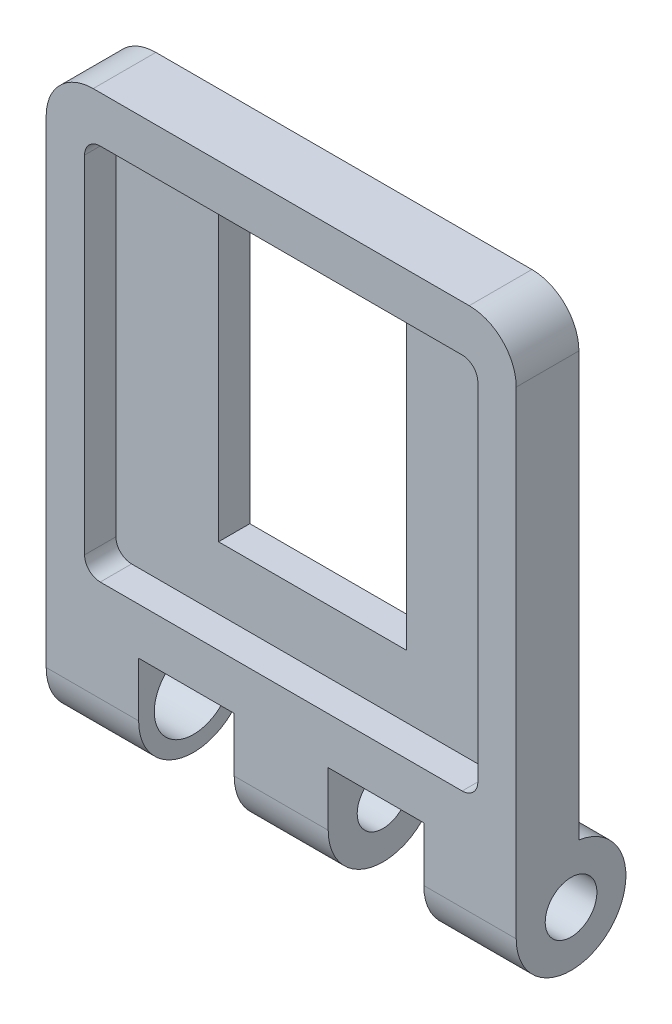
SolidWorks part; units mm, degrees
ref_plane "Front Plane" through (0, 0, 0) normal (0, 0, 1) x (1, 0, 0)
ref_plane "Top Plane" through (0, 0, 0) normal (0, 1, 0) x (1, 0, 0)
ref_plane "Right Plane" through (0, 0, 0) normal (1, 0, 0) x (0, 0, -1)
sketch "Croquis1" plane through (0, 0, 0) normal (0, 0, 1) x (1, 0, 0)
  line L1 (-11.55, 12.05) -> (11.55, 12.05)
  line L2 (-12.55, 11.05) -> (-12.55, -11.05)
  line L3 (-11.55, -12.05) -> (11.55, -12.05)
  line L4 (12.55, 11.05) -> (12.55, -11.05)
  line L5 (-12.55, 12.05) -> (12.55, -12.05) construction
  line L6 (-12.55, -12.05) -> (12.55, 12.05) construction
  line L11 (-6, 12.05) -> (6, 12.05)
  line L12 (-6, 12.05) -> (-6, -8.05)
  line L13 (-6, -8.05) -> (6, -8.05)
  line L14 (6, 12.05) -> (6, -8.05)
  line L15 (-6, 12.05) -> (6, -8.05) construction
  line L16 (-6, -8.05) -> (6, 12.05) construction
  line L21 (-12, 15) -> (12, 15)
  line L22 (-15, 12) -> (-15, -15)
  line L23 (-15, -15) -> (15, -15)
  line L24 (15, 12) -> (15, -15)
  line L25 (-15, 15) -> (15, -15) construction
  line L26 (-15, -15) -> (15, 15) construction
  arc A0 (-12.55, -11.05) -> (-11.55, -12.05) centre (-11.55, -11.05) ccw
  arc A1 (11.55, -12.05) -> (12.55, -11.05) centre (11.55, -11.05) ccw
  arc A2 (11.55, 12.05) -> (12.55, 11.05) centre (11.55, 11.05) cw
  arc A3 (-11.55, 12.05) -> (-12.55, 11.05) centre (-11.55, 11.05) ccw
  arc A8 (12, 15) -> (15, 12) centre (12, 12) cw
  arc A11 (-12, 15) -> (-15, 12) centre (-12, 12) ccw
  point P0 (0, 0)
  point P21 (0, 0)
  point P23 (15, -14.6547)
  point P24 (15.2675, -15)
  point P25 (-14.7997, -15.0672)
  point P26 (-14.8799, -14.8799)
  point P30 (0, 2)
  point P35 (14.9616, -14.9616)
  point P37 (0, 0)
  dimension "D3" = 1
  dimension "D8" = 3
  dimension "D1" = 25.1
  dimension "D2" = 24.1
  dimension "D5" = 4
  dimension "D6" = 12
  dimension "D4" = 30
  dimension "D7" = 30
extrude "Saliente-Extruir1" add sketch "Croquis1" along normal blind 2 contours L1 A3 L2 A0 L3 A1 L4 A2 L14 L13 L12 region at (-8.775, 11.702, 0)
extrude "Saliente-Extruir2" add sketch "Croquis1<3>" along normal blind 4 contours A3 L1 A2 L4 A1 L3 A0 L2 region at (0, 14.5757, 0)
sketch "Croquis1<3>" plane through (0, 0, 0) normal (0, 0, 1) x (1, 0, 0) same geometry as "Croquis1"
sketch "Croquis2" plane through (15, 0, 0) normal (1, 0, 0) x (0, 0, -1)
  line L0 (0, -15) -> (0, -15.0359)
  line L1 (0, -15) -> (-0.5, -15)
  line L2 (-0.5, -15) -> (-4, -15)
  line L3 (-4, -15) -> (-4, -18.5)
  line L5 (-4, -15) -> (0, -15) construction
  circle A0 centre (-0.5, -18.5) radius 3.5
  circle A1 centre (-0.5, -18.5) radius 2.5
  circle A2 centre (-0.5, -18.5) radius 1.65
  line M13 (-4, -15) -> (0, -15)
  dimension "D1" = 7
  dimension "D2" = 5
  dimension "D3" = 3.3
extrude "Saliente-Extruir3" add sketch "Croquis2" against normal up to surface (30 mm away) contours A0 L2 L3 M13 | A0 L0 M13 | A0 | A2 region at (15, -15.0108, 0.1249) region at (15, -15.7818, 3.2182) up to face at (-15, -1.5, 2)
sketch "Croquis3" plane through (0, 0, 0) normal (0, 0, 1) x (1, 0, 0)
  line L1 (-9.1, -15.0359) -> (-3, -15.0359)
  line L2 (-9.1, -15.0359) -> (-9.1, -22)
  line L3 (-9.1, -22) -> (-3, -22)
  line L4 (-3, -15.0359) -> (-3, -22)
  line L5 (-15, -22) -> (15, -22) construction
  line L6 (-15, -15.0359) -> (-15, -22) construction
  line L7 (3, -15.0359) -> (9.1, -15.0359)
  line L8 (3, -15.0359) -> (3, -22)
  line L9 (3, -22) -> (9.1, -22)
  line L10 (9.1, -15.0359) -> (9.1, -22)
  line L11 (15, -22) -> (15, -15.0359) construction
  line L14 (-15, -15.0359) -> (15, -15.0359) construction
  dimension "D1" = 6.1
  dimension "D2" = 6.1
  dimension "D3" = 5.9
  dimension "D4" = 5.9
extrude "Cortar-Extruir1" cut sketch "Croquis3" against normal through all both and the other way through all
extrude "Cortar-Extruir3" cut sketch "Croquis2<3>" along normal up to surface (-24.1 mm away) and the other way through all from surface contours A1 A2 region at (15, -18.5, 2.9293) up to face at (-9.1, -17.6499, 1.4029) starting at face at (-15, -3.4784, 1.0522)
sketch "Croquis2<3>" plane through (15, 0, 0) normal (1, 0, 0) x (0, 0, -1) same geometry as "Croquis2"
